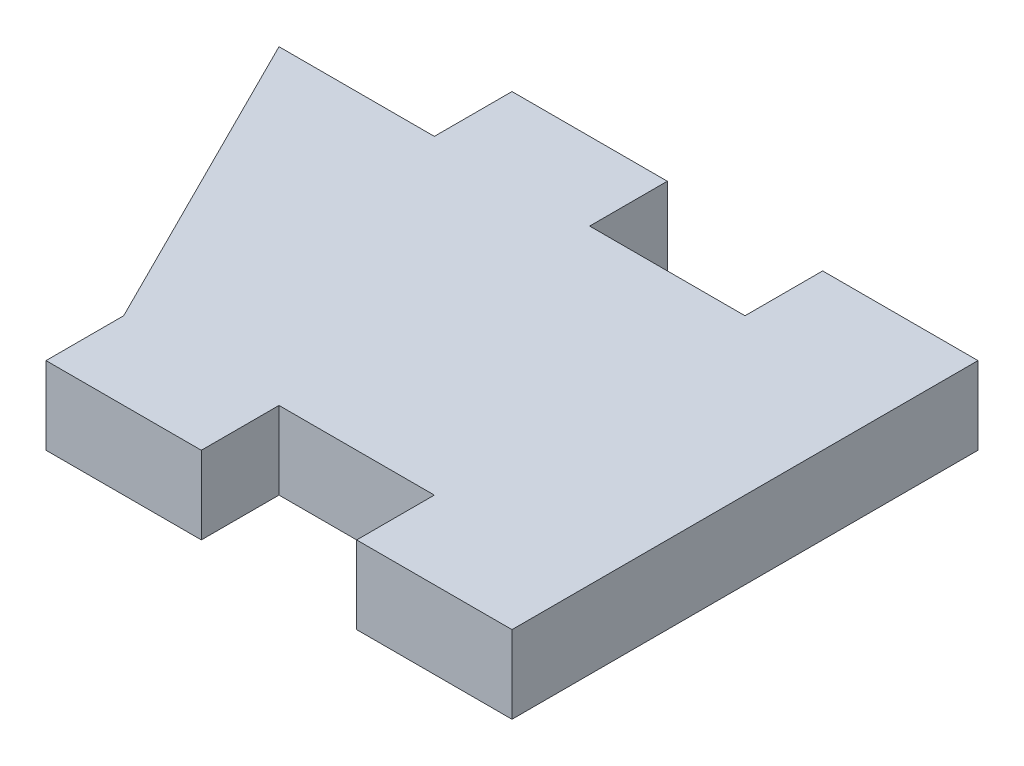
SolidWorks part; units mm, degrees
ref_plane "Front Plane" through (0, 0, 0) normal (0, 0, 1) x (1, 0, 0)
ref_plane "Top Plane" through (0, 0, 0) normal (0, 1, 0) x (1, 0, 0)
ref_plane "Right Plane" through (0, 0, 0) normal (1, 0, 0) x (0, 0, -1)
sketch "Sketch1" plane through (0, 0, 0) normal (0, 1, 0) x (1, 0, 0)
  line L1 (-12.7, 6.35) -> (12.7, 6.35)
  line L2 (-12.7, 6.35) -> (-12.7, -6.35)
  line L3 (-12.7, -6.35) -> (12.7, -6.35)
  line L4 (12.7, 6.35) -> (12.7, -6.35)
  dimension "D1" = 25.4
  dimension "D2" = 12.7
  dimension "D3" = 6.35
  dimension "D4" = 12.7
extrude "Boss-Extrude1" add sketch "Sketch1" along normal blind 3.175
sketch "Sketch2" plane through (0, 0, 6.35) normal (0, 0, 1) x (1, 0, 0)
  line L0 (-12.7, 0) -> (12.7, 0) construction
  line L1 (12.7, 3.175) -> (6.35, 3.175)
  line L2 (12.7, 3.175) -> (12.7, 0)
  line L3 (12.7, 0) -> (6.35, 0)
  line L4 (6.35, 3.175) -> (6.35, 0)
  line L5 (-12.7, 3.175) -> (12.7, 3.175) construction
  line L6 (0, 3.175) -> (-6.35, 3.175)
  line L7 (0, 3.175) -> (0, 0)
  line L8 (0, 0) -> (-6.35, 0)
  line L9 (-6.35, 3.175) -> (-6.35, 0)
  dimension "D1" = 6.35
  dimension "D2" = 6.35
  dimension "D3" = 6.35
extrude "Boss-Extrude2" add sketch "Sketch2" along normal blind 3.175
mirror "Mirror1" about plane through (0, 0, 0) normal (0, 0, 1) of "Boss-Extrude2"
sketch "Sketch3" plane through (0, 3.175, 0) normal (0, 1, 0) x (1, 0, 0)
  line L0 (-6.35, -6.35) -> (-12.7, 6.35)
  line L1 (-12.7, 6.35) -> (-12.7, -6.35)
  line L2 (-12.7, -6.35) -> (-6.35, -6.35) construction
  line L3 (-12.7, 6.35) -> (-12.7, -6.35) construction
  line L4 (-12.7, -6.35) -> (-6.35, -6.35)
extrude "Cut-Extrude1" cut sketch "Sketch3" against normal blind 3.175
